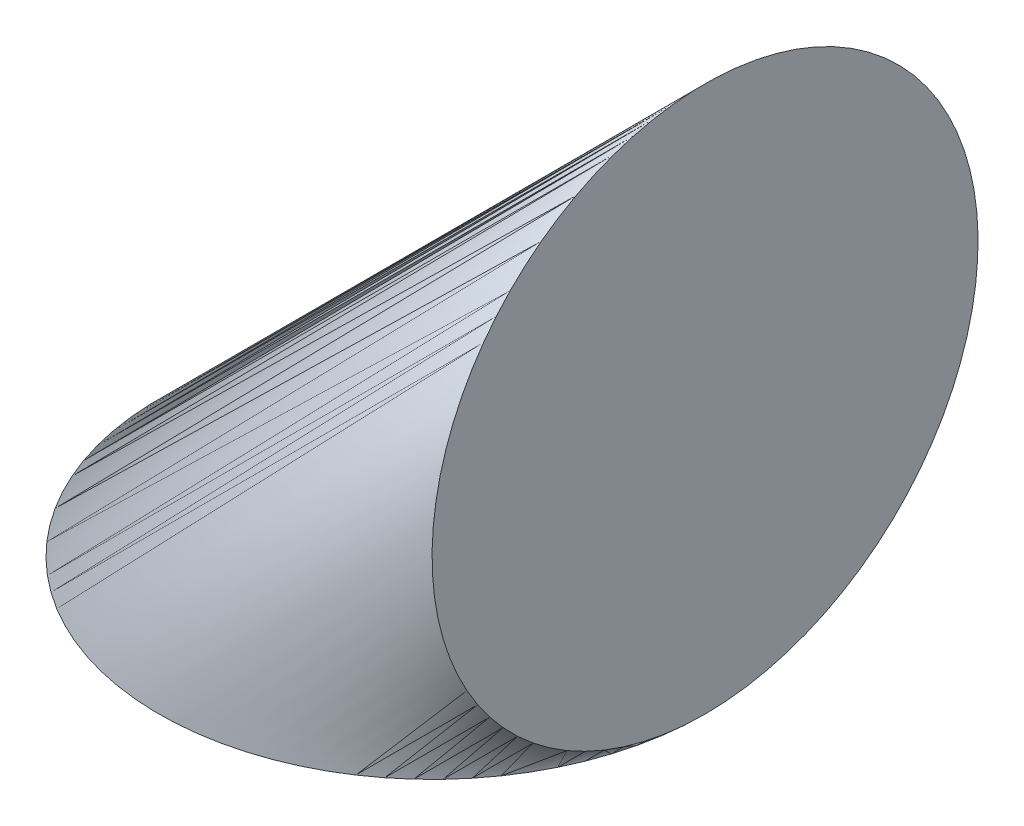
SolidWorks part; units mm, degrees
material "1060 Alloy"
ref_plane "Front Plane" through (0, 0, 0) normal (0, 0, 1) x (1, 0, 0)
ref_plane "Top Plane" through (0, 0, 0) normal (0, 1, 0) x (1, 0, 0)
ref_plane "Right Plane" through (0, 0, 0) normal (1, 0, 0) x (0, 0, -1)
sketch "Sketch2" plane through (0, 0, 0) normal (0, 1, 0) x (1, 0, 0)
  circle A0 centre (0, 0) radius 50
  dimension "D1" = 100
sketch "Sketch4" plane through (0, 0, 0) normal (0, 0, 1) x (1, 0, 0)
  line L0 (50, 0) -> (-50, 0) construction
  line L1 (50, 0) -> (-50, 0) construction
  line L2 (50, 50) -> (50, 0) construction
  arc A0 (0, 0) -> (50, 50) centre (50, 0) cw
sweep "Sweep1" add profiles "Sketch2" path "Sketch4"
ref_axis "Axis1" through (50, 50, 0) along (1, 0, 0)
ref_axis "Axis2" through (0, 0, 0) along (0, -1, 0)
